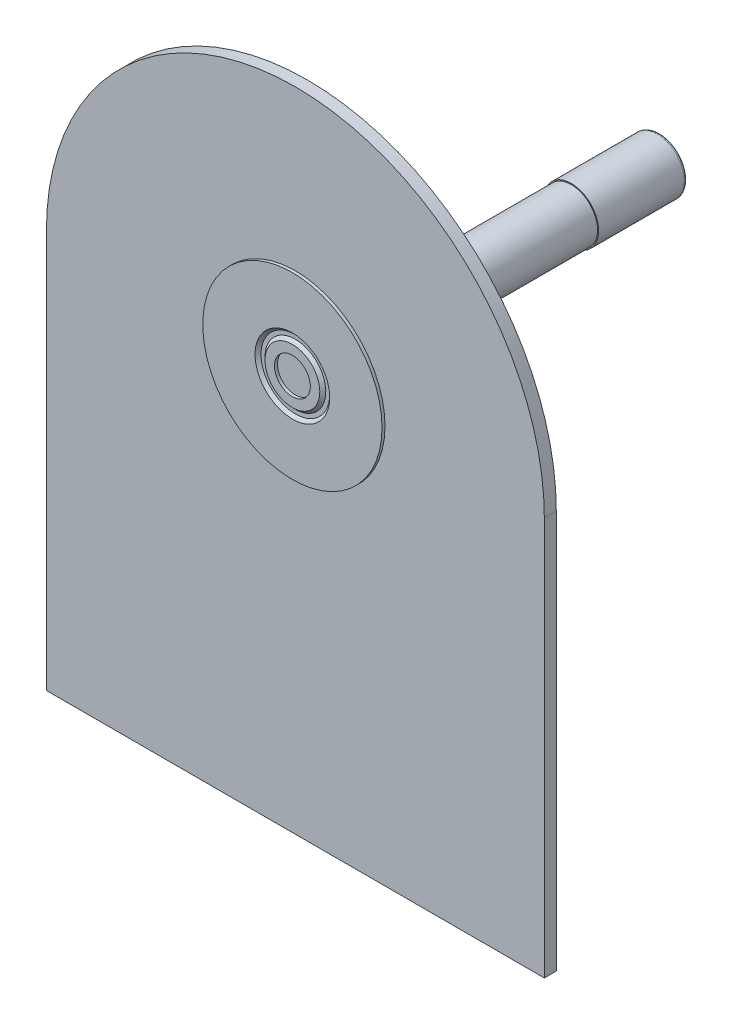
SolidWorks part; units mm, degrees
material "45"
ref_plane "前视基准面" through (0, 0, 0) normal (0, 0, 1) x (1, 0, 0)
ref_plane "上视基准面" through (0, 0, 0) normal (0, 1, 0) x (1, 0, 0)
ref_plane "右视基准面" through (0, 0, 0) normal (1, 0, 0) x (0, 0, -1)
sketch "草图1" plane through (0, 0, 0) normal (0, 0, 1) x (1, 0, 0)
  circle A0 centre (0, 0) radius 27.5
  dimension "D1" = 55
extrude "凸台-拉伸1" add sketch "草图1" along normal blind 90
sketch "草图2" plane through (0, 0, 90) normal (0, 0, 1) x (1, 0, 0)
  circle A0 centre (0, 0) radius 26.5
  dimension "D1" = 53
extrude "凸台-拉伸2" add sketch "草图2" along normal blind 190
sketch "草图3" plane through (0, 0, 280) normal (0, 0, 1) x (1, 0, 0)
  circle A0 centre (0, 0) radius 27.5
  dimension "D1" = 55
extrude "凸台-拉伸3" add sketch "草图3" along normal blind 60
sketch "草图4" plane through (0, 0, 340) normal (0, 0, 1) x (1, 0, 0)
  circle A0 centre (0, 0) radius 32.5
  dimension "D1" = 65
extrude "凸台-拉伸4" add sketch "草图4" along normal blind 30
sketch "草图5" plane through (0, 0, 370) normal (0, 0, 1) x (1, 0, 0)
  circle A0 centre (0, 0) radius 150
  dimension "D1" = 300
extrude "凸台-拉伸5" add sketch "草图5" against normal blind 20 separate body
sketch "草图6" plane through (0, 0, 350) normal (0, 0, -1) x (-1, 0, 0)
  circle A0 centre (0, 0) radius 32.5
  dimension "D1" = 65
extrude "切除-拉伸1" cut sketch "草图6" against normal blind 20
chamfer "倒角4" distance 5 angle 45 1 edges at (-32.5, 0, 350)
sketch "草图8" plane through (0, 0, 370) normal (0, 0, 1) x (1, 0, 0)
  circle A1 centre (0, 0) radius 90
  dimension "D1" = 180
extrude "切除-拉伸2" cut sketch "草图8" against normal blind 3 flip side to cut
chamfer "倒角5" distance 5 angle 45 1 edges at (32.5, 0, 370)
chamfer "倒角6" distance 5 angle 45 1 edges at (-32.5, 0, 370)
hole_wizard "M12 螺纹孔1" positions "草图10" profile "草图9" tap size "M12" standard "GB"
sketch "草图10" plane through (0, 0, 0) normal (0, 0, -1) x (-1, 0, 0)
  circle A0 centre (0, 0) radius 27.5 construction
  point P0 (0, 0)
  dimension "D1" = 0
sketch "草图9" plane through (0, 0, 0) normal (1, 0, 0) x (0, 1, 0)
  line L0 (0, 0) -> (0, 32.3144)
  line L1 (0, 32.3144) -> (5.1, 29.25)
  line L2 (5.1, 29.25) -> (5.1, 0)
  line L5 (5.1, 0) -> (0, 0)
  line L10 (0, 32.3144) -> (-5.1, 29.25) construction
  line L11 (0, -6.35) -> (0, 107.95) construction
  dimension "螺纹孔钻头直径" = 10.2
  dimension "螺纹孔钻头深度" = 29.25
  dimension "导头角度" = 118
cosmetic thread "孔螺蚊线1" parameters "D1"=24, "D2"=12
ref_plane "基准面1" through (0, 26.5, 0) normal (0, 1, 0) x (-1, 0, 0)
sketch "草图12" plane through (0, 0, 350) normal (0, 0, -1) x (-1, 0, 0)
  circle A0 centre (0, 0) radius 5.1 construction
  circle A1 centre (0, 127.5) radius 3
  dimension "D1" = 127.5
  dimension "D2" = 6
extrude "切除-拉伸4" cut sketch "草图12" against normal through all
pattern_circular "阵列(圆周)1" count 8 over 360 about axis through (0, 0, 280) along (0, 0, -1) of "切除-拉伸4"
sketch "草图13" plane through (0, 0, 0) normal (0, 0, -1) x (-1, 0, 0)
  circle A0 centre (0, 0) radius 18
  dimension "D1" = 36
extrude "切除-拉伸5" cut sketch "草图13" against normal through all
fillet "圆角1" radius 10 1 edges at (-18, 0, 0)
fillet "圆角2" radius 3 1 edges at (27.5, 0, 0)
hole_wizard "M12 螺纹孔2" positions "草图16" profile "草图15" tap size "M12" standard "Gb"
sketch "草图16" plane through (0, 0, 367) normal (0, 0, 1) x (1, 0, 0)
  point P0 (0, 127.5)
sketch "草图15" plane through (0, 127.5, 367) normal (1, 0, 0) x (0, -1, 0)
  line L0 (0, 0) -> (0, 32.3144)
  line L1 (0, 32.3144) -> (5.1, 29.25)
  line L2 (5.1, 29.25) -> (5.1, 0)
  line L5 (5.1, 0) -> (0, 0)
  line L10 (0, 32.3144) -> (-5.1, 29.25) construction
  line L11 (0, -6.35) -> (0, 107.95) construction
  dimension "螺纹孔钻头直径" = 10.2
  dimension "螺纹孔钻头深度" = 29.25
  dimension "导头角度" = 118
cosmetic thread "孔螺蚊线2" parameters "D1"=17, "D2"=12
pattern_circular "阵列(圆周)2" count 8 over 360 about axis through (0, 0, 350) along (0, 0, 1) of "M12 螺纹孔2"
sketch "草图17" plane through (0, 0, 367) normal (0, 0, 1) x (1, 0, 0)
  line L0 (-250, 0) -> (-250, -400)
  line L1 (-250, -400) -> (250, -400)
  line L2 (250, -400) -> (250, 0)
  arc A0 (250, 0) -> (-250, 0) centre (0, 0) ccw
  dimension "D1" = 500
  dimension "D2" = 400
extrude "凸台-拉伸6" add sketch "草图17" against normal blind 12 separate body
